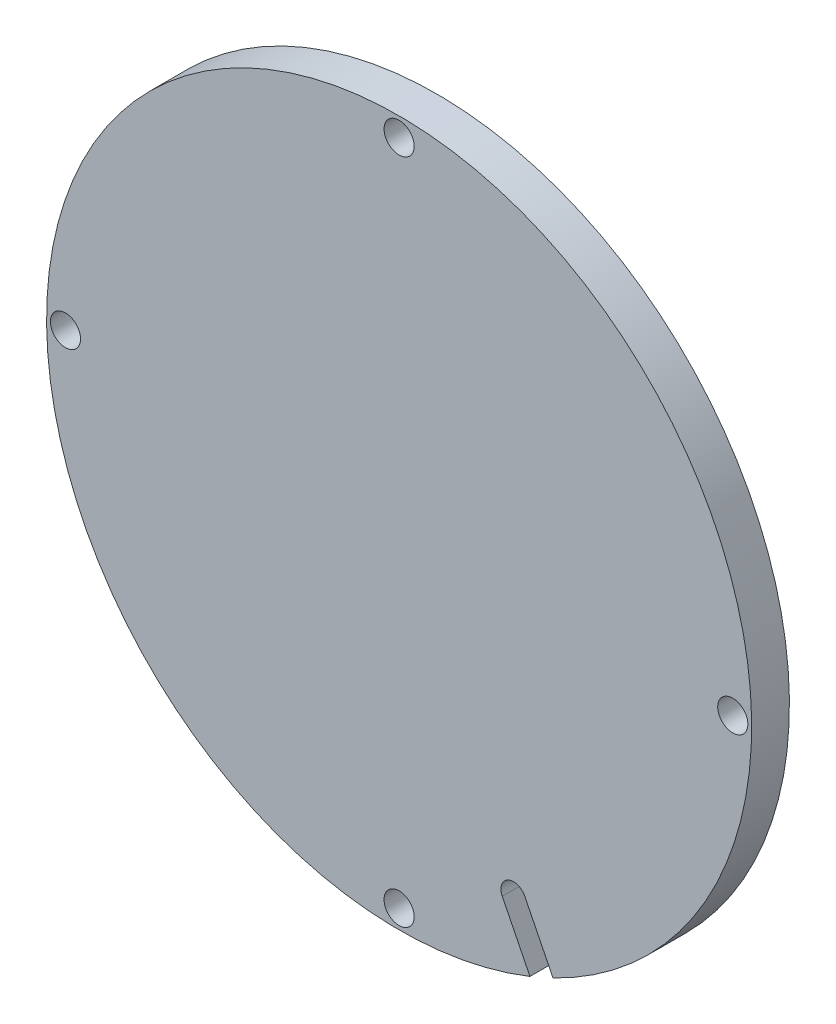
SolidWorks part; units mm, degrees
ref_plane "Front Plane" through (0, 0, 0) normal (0, 0, 1) x (1, 0, 0)
ref_plane "Top Plane" through (0, 0, 0) normal (0, 1, 0) x (1, 0, 0)
ref_plane "Right Plane" through (0, 0, 0) normal (1, 0, 0) x (0, 0, -1)
sketch "Sketch2" plane through (0, 0, 0) normal (0, 0, 1) x (1, 0, 0)
  circle A0 centre (0, 0) radius 44.45
  dimension "D1" = 88.9
extrude "Boss-Extrude1" add sketch "Sketch2" along normal blind 4.7625 contours A0
hole_wizard "#6 Clearance Hole1" positions "Sketch3" profile "Sketch4" hole size "#6" standard "ANSI Inch" end condition up to next
sketch "Sketch3" plane through (0, 0, 4.7625) normal (0, 0, 1) x (1, 0, 0)
  circle A0 centre (0, 0) radius 44.45 construction
  point P0 (0, 42.0688)
  dimension "D1" = 42.0688
sketch "Sketch4" plane through (0, 42.0688, 4.7625) normal (1, 0, 0) x (0, -1, 0)
  line L0 (0, 0) -> (0, 4.7635)
  line L1 (0, 4.7635) -> (1.8986, 4.7635)
  line L2 (1.8986, 4.7635) -> (1.8986, 0)
  line L5 (1.8986, 0) -> (0, 0)
  line L11 (0, -6.35) -> (0, 107.95) construction
  dimension "Thru Hole Dia." = 3.7973
  dimension "Thru Hole Depth" = 4.7635
pattern_circular "CirPattern1" count 4 over 360 about axis through (0, 0, 4.7625) along (0, 0, 1) of "#6 Clearance Hole1"
sketch "Sketch5" plane through (0, 0, 4.7625) normal (0, 0, 1) x (1, 0, 0)
  line L0 (17.9605, -40.6598) -> (14.423, -33.5542) construction
  line L1 (16.5394, -41.3673) -> (13.0019, -34.2617)
  line L2 (19.3816, -39.9523) -> (15.8441, -32.8467)
  circle A0 centre (0, 0) radius 44.45 construction
  arc A1 (16.5394, -41.3673) -> (19.3816, -39.9523) centre (17.9605, -40.6598) ccw
  arc A2 (15.8441, -32.8467) -> (13.0019, -34.2617) centre (14.423, -33.5542) ccw
  point P4 (16.1917, -37.107)
  dimension "D1" = 3.175
  dimension "D2" = 7.9375
extrude "Cut-Extrude1" cut sketch "Sketch5" against normal through all both and the other way through all contours L2 A2 L1 A1
